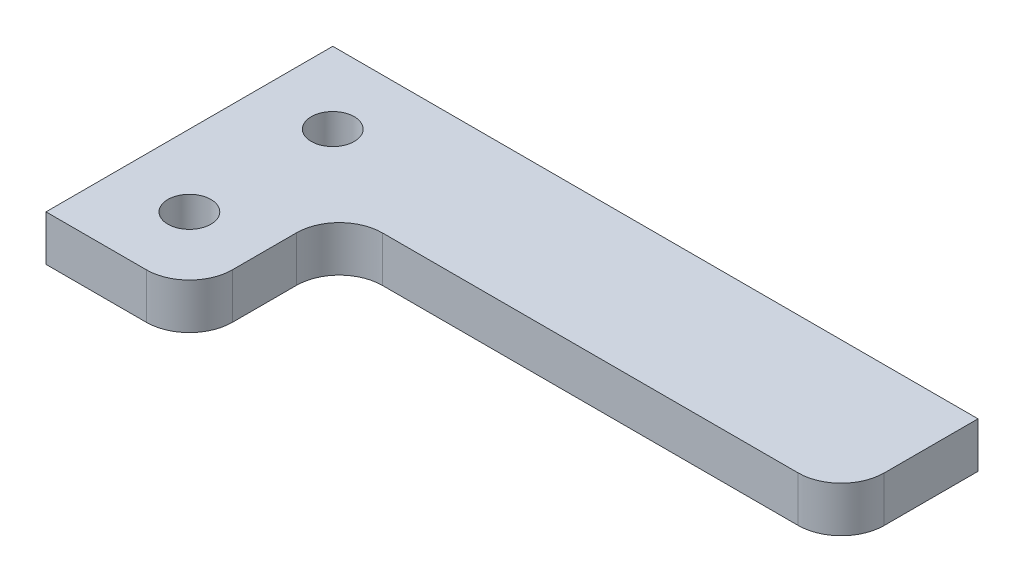
SolidWorks part; units mm, degrees
ref_plane "Front Plane" through (0, 0, 0) normal (0, 0, 1) x (1, 0, 0)
ref_plane "Top Plane" through (0, 0, 0) normal (0, 1, 0) x (1, 0, 0)
ref_plane "Right Plane" through (0, 0, 0) normal (1, 0, 0) x (0, 0, -1)
sketch "Sketch1" plane through (0, 0, 0) normal (0, 1, 0) x (1, 0, 0)
  line L0 (0, 0) -> (45, 0)
  line L1 (45, 0) -> (45, -6.5394)
  line L2 (42, -9.5394) -> (13, -9.5394)
  line L3 (0, -20) -> (7, -20)
  line L4 (0, -20) -> (0, 0)
  line L5 (10, -17) -> (10, -12.5394)
  arc A0 (10, -17) -> (7, -20) centre (7, -17) cw
  arc A1 (10, -12.5394) -> (13, -9.5394) centre (13, -12.5394) cw
  arc A2 (45, -6.5394) -> (42, -9.5394) centre (42, -6.5394) cw
  dimension "D5" = 3
  dimension "D1" = 45
  dimension "D2" = 20
  dimension "D3" = 10
  dimension "D4" = 10
extrude "Boss-Extrude1" add sketch "Sketch1" along normal blind 3.175
hole_wizard "Ø3.0 (3) Diameter Hole1" positions "Sketch3" profile "Sketch2" hole size "Ø3.0" standard "Ansi Metric"
sketch "Sketch3" plane through (0, 3.175, 0) normal (0, 1, 0) x (-1, 0, 0)
  line L0 (-5, 15) -> (-5, 5) construction
  line L2 (0, 0) -> (0, 20) construction
  line L3 (-45, 0) -> (0, 0) construction
  point P0 (-5, 5)
  point P1 (-5, 15)
  point P14 (-5, 6.2344)
  dimension "D1" = 5
  dimension "D2" = 5
  dimension "D3" = 10
sketch "Sketch2" plane through (5, 3.175, 5) normal (1, 0, 0) x (0, 0, 1)
  line L0 (0, 0) -> (0, 10.9013)
  line L1 (0, 10.9013) -> (1.5, 10)
  line L2 (1.5, 10) -> (1.5, 0)
  line L5 (1.5, 0) -> (0, 0)
  line L10 (0, 10.9013) -> (-1.5, 10) construction
  line L11 (0, -6.35) -> (0, 107.95) construction
  dimension "Hole Dia." = 3
  dimension "Hole Depth" = 10
  dimension "Drill Angle" = 118
